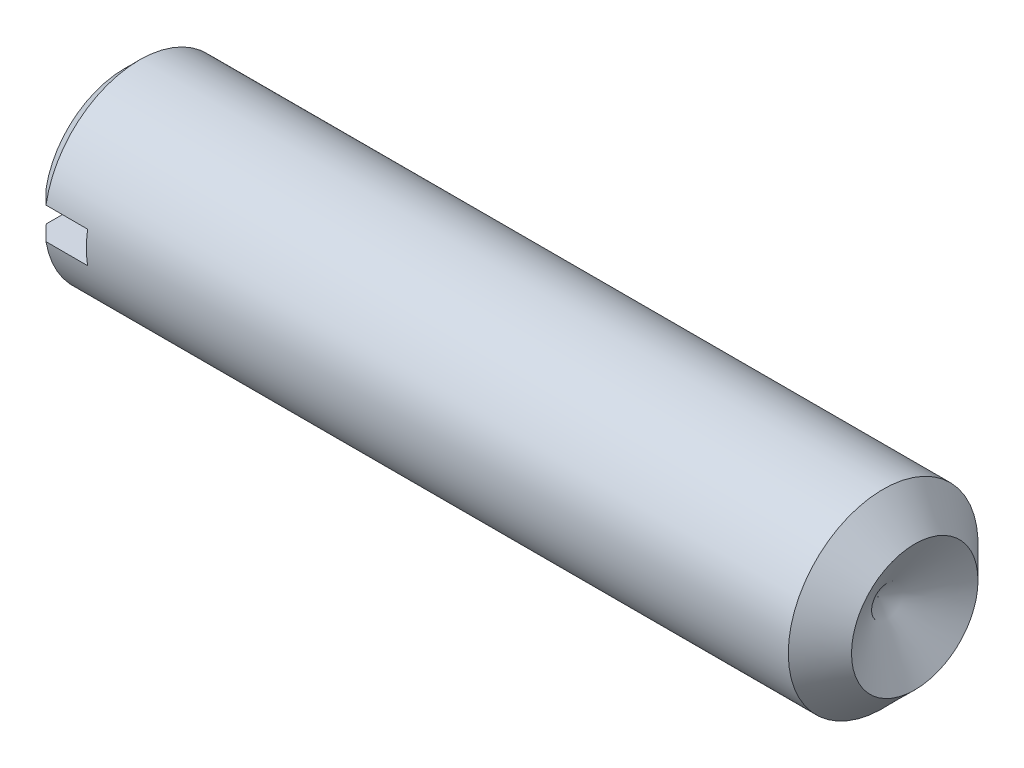
SolidWorks part; units mm, degrees
ref_plane "Front Plane" through (0, 0, 0) normal (0, 0, 1) x (1, 0, 0)
ref_plane "Top Plane" through (0, 0, 0) normal (0, 1, 0) x (1, 0, 0)
ref_plane "Right Plane" through (0, 0, 0) normal (1, 0, 0) x (0, 0, -1)
sketch "BodySke" plane through (0, 0, 0) normal (0, 0, 1) x (1, 0, 0)
  line L0 (0, 0) -> (88.3411, 0) construction
  line L1 (0, 0) -> (0, 5.036)
  line L2 (0, 5.036) -> (0.964, 6)
  line L3 (0.964, 6) -> (48, 6)
  line L4 (50, 4) -> (48, 6)
  line L5 (0, -5.036) -> (0.964, -6) construction
  line L6 (47.6906, 0) -> (0, 0)
  line L7 (1.75, 0) -> (1.75, 8.5388) construction
  line L8 (50, 4) -> (47.6906, 0)
  line L9 (50, -4) -> (47.6906, 0) construction
  dimension "Thread_minor" = 10.072
  dimension "Length" = 50
  dimension "Drive_chamfer_angle" = 90
  dimension "Advance" = 1.75
revolve "BaseBody" add sketch "BodySke" angle 360 about L0
cosmetic thread "ThreadCosmetic" [suppressed] parameters "Thread_minor"=10.072
sketch "SlotSke" plane through (0, 0, 0) normal (1, 0, 0) x (0, 0, -1)
  line L0 (-6, 1) -> (6, -1) construction
  line L1 (-6, 1) -> (6, 1)
  line L2 (-6, 1) -> (-6, -1)
  line L3 (-6, -1) -> (6, -1)
  line L4 (6, 1) -> (6, -1)
  dimension "D1" = 12
extrude "Slot" cut sketch "SlotSke" along normal blind 3.6
sketch "ThdSchSke" plane through (0, 0, 0) normal (0, 0, 1) x (1, 0, 0)
  line L0 (0, 0) -> (53.6961, 0) construction
  line L1 (1.6009, 7.1131) -> (1.6009, 6)
  line L2 (1.6009, 7.1131) -> (2.714, 7.1131)
  line L3 (2.714, 7.1131) -> (2.714, 6)
  line L4 (2.714, 6) -> (2.1574, 5.036)
  line L5 (2.1574, 5.036) -> (1.6009, 6)
  dimension "D1" = 1.75
revolve "ThreadSchematic" [suppressed] cut sketch "ThdSchSke" angle 360 about L0
pattern_linear "ThdSchPat" [suppressed] of bodies 115
equation "\"Thread_minor@ThreadCosmetic\" = \"Thread_minor@BodySke\""
equation "\"D1@SlotSke\" = \"Diameter@BodySke\""
equation "\"D1@ThdSchSke\" = \"Advance@BodySke\""
equation "\"Advance@ThdSchPat\" = \"Advance@BodySke\""
equation "\"Tooth_Num@ThdSchPat\" =  int( \"Length@BodySke\" / \"Advance@BodySke\" )  - 1"
